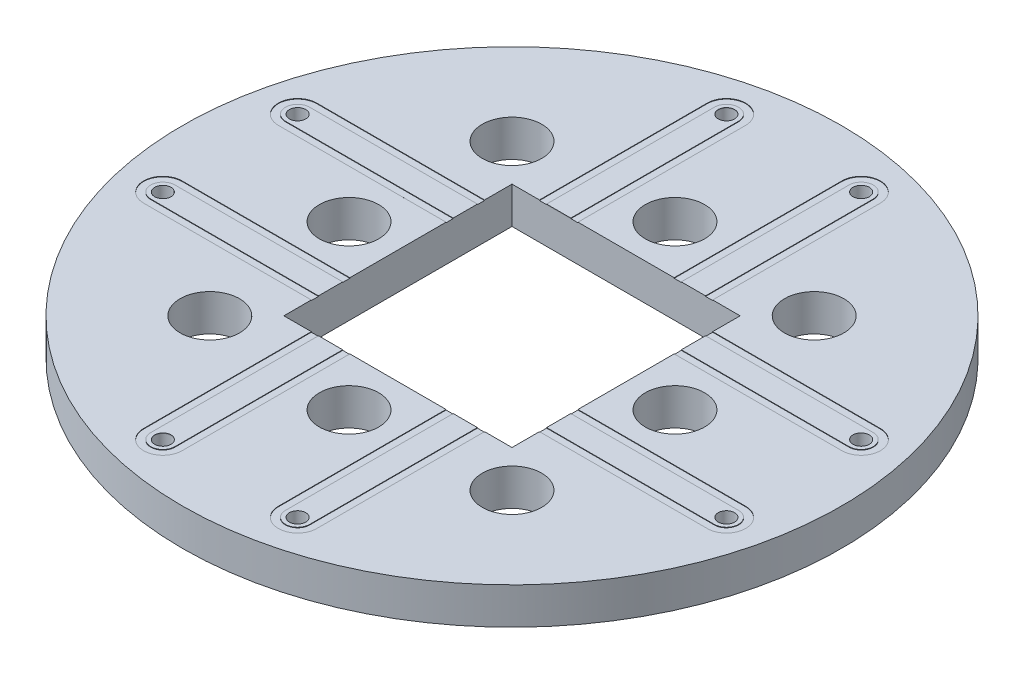
SolidWorks part; units mm, degrees
material "Ceramic Porcelain"
ref_plane "Front Plane" through (0, 0, 0) normal (0, 0, 1) x (1, 0, 0)
ref_plane "Top Plane" through (0, 0, 0) normal (0, 1, 0) x (1, 0, 0)
ref_plane "Right Plane" through (0, 0, 0) normal (1, 0, 0) x (0, 0, -1)
ref_axis "Y Axis" through (0, 0.0762, 0) along (0, -1, 0)
sketch "Boday Sketch" plane through (0, 0, 0) normal (0, 1, 0) x (1, 0, 0)
  circle A0 centre (0, 0) radius 11.557
  dimension "D1" = 23.114
extrude "Body" add sketch "Boday Sketch" against normal blind 1.27
sketch "Copper Sketch" plane through (0, 0, 0) normal (0, 1, 0) x (1, 0, 0)
  circle A0 centre (0, 0) radius 11.557
  dimension "D1" = 23.114
extrude "Copper" add sketch "Copper Sketch" along normal blind 0.0175
sketch "IO Hole Positions" plane through (0, 0, 0) normal (0, 1, 0) x (1, 0, 0)
  line L0 (-11.557, 0) -> (11.557, 0) construction
  circle A1 centre (0, 0) radius 11.557 construction
  point P1 (-2.3622, 9.8816)
  point P8 (-2.3622, -9.8816)
  dimension "D2" = 2.3622
sketch "Gap" plane through (0, 0, 0) normal (0, 1, 0) x (1, 0, 0)
  line L10 (-3.0372, 9.8816) -> (-3.0372, -9.8816)
  line L11 (-11.557, 0) -> (11.557, 0) construction
  line L12 (-3.0372, 0) -> (-1.6872, 0) construction
  line L13 (-1.6872, -9.8816) -> (-1.6872, 9.8816)
  arc A5 (-1.6872, 9.8816) -> (-3.0372, 9.8816) centre (-2.3622, 9.8816) ccw
  arc A6 (-1.6872, -9.8816) -> (-3.0372, -9.8816) centre (-2.3622, -9.8816) cw
  dimension "D1" = 0.675
sketch "Center Sketch" plane through (0, 0, 0) normal (0, 1, 0) x (1, 0, 0)
  line L6 (-2.7872, 9.8816) -> (-2.7872, -9.8816)
  line L7 (-11.557, 0) -> (11.557, 0) construction
  line L8 (-2.7872, 0) -> (-1.9372, 0) construction
  line L9 (-1.9372, -9.8816) -> (-1.9372, 9.8816)
  arc A3 (-1.9372, 9.8816) -> (-2.7872, 9.8816) centre (-2.3622, 9.8816) ccw
  arc A4 (-1.9372, -9.8816) -> (-2.7872, -9.8816) centre (-2.3622, -9.8816) cw
  dimension "D1" = 0.425
extrude "Gap Cut" cut sketch "Gap" along normal through all
extrude "Center" add sketch "Center Sketch" along normal blind 0.0175 separate body
sketch "IO Hole Sketch" plane through (0, 0, 0) normal (0, 1, 0) x (1, 0, 0)
  circle A1 centre (-2.3622, 9.8816) radius 0.287
  circle A3 centre (-2.3622, -9.8816) radius 0.287
  circle A4 centre (0, 0) radius 10.16 construction
  dimension "D1" = 0.574
  dimension "D2" = 0.574
  dimension "D3" = 20.32
  dimension "D4" = 2.3622
extrude "IO Hole" cut sketch "IO Hole Sketch" against normal through all and the other way through all
pattern_circular "Gap Cuts" count 4 over 360 about axis through (0, 0.0762, 0) along (0, -1, 0) of "Gap Cut"
pattern_circular "Centers" count 4 over 360 about axis through (0, 0.0762, 0) along (0, -1, 0) of "Center"
pattern_circular "IO Holes" count 4 over 360 about axis through (0, 0.0762, 0) along (0, -1, 0) of "IO Hole"
sketch "Pocket Sketch" plane through (0, 0, 0) normal (0, 1, 0) x (1, 0, 0)
  line L1 (-4, -4) -> (4, -4)
  line L2 (-4, -4) -> (-4, 4)
  line L3 (-4, 4) -> (4, 4)
  line L4 (4, -4) -> (4, 4)
  line L5 (-4, -4) -> (4, 4) construction
  line L6 (-4, 4) -> (4, -4) construction
  point P0 (0, 0)
  dimension "D1" = 8
  dimension "D2" = 8
extrude "Pocket" cut sketch "Pocket Sketch" against normal through all and the other way through all
sketch "Posts" plane through (0, 0, 0) normal (0, 1, 0) x (1, 0, 0)
  circle A0 centre (0, 5.715) radius 1.0414
  circle A8 centre (-5.2984, 5.2984) radius 1.0414
  point P0 (0, 5.715)
  point P4 (-5.2984, 5.2984)
  dimension "D2" = 2.0828
  dimension "D4" = 2.0828
  dimension "D1" = 5.715
  dimension "D3" = 7.493
  dimension "D5" = 5.715
extrude "Post Cut" cut sketch "Posts" against normal through all and the other way through all
pattern_circular "Post Cuts" count 4 over 360 about axis through (0, 0.0762, 0) along (0, -1, 0) of "Post Cut"
equation "\"mount_d\"= 0.91in"
equation "\"dieletric_h\"= 0.05in"
equation "\"D1@Boday Sketch\" = \"mount_d\""
equation "\"D1@Body\" = \"dieletric_h\""
equation "\"screw_inner_r\"= 0.415in"
equation "\"io_r\"= 0.4in"
equation "\"io_hole_d\"= 0.574mm"
equation "\"W\"= 0.85mm"
equation "\"G\"= 0.25mm"
equation "\"copper_t\"= 17.5um"
equation "\"silicon_size\"= 8mm"
equation "\"D1@Center\" = \"copper_t\""
equation "\"D1@Copper\"=\"copper_t\""
equation "\"D1@Pocket Sketch\" = \"silicon_size\""
equation "\"D2@Pocket Sketch\" = \"silicon_size\""
equation "\"post_r1\" = 0.225in"
equation "\"post_r2\" = 0.295in"
equation "\"D1@Posts\"=\"post_r1\""
equation "\"post_hole_size\"= 0.082in"
equation "\"D2@Posts\"=\"post_hole_size\""
equation "\"D3@Posts\"=\"post_r2\""
equation "\"D4@Posts\"=\"post_hole_size\""
equation "\"io_x\"= 0.093in"
equation "\"D1@IO Hole Positions\"=\"io_r\""
equation "\"D2@IO Hole Positions\"=\"io_x\""
equation "\"D1@IO Hole Sketch\"=\"io_hole_d\""
equation "\"D2@IO Hole Sketch\"=\"io_hole_d\""
equation "\"D1@Gap\"= \"W\" / 2 + \"G\""
equation "\"D1@Center Sketch\"=\"W\" / 2"
equation "\"D5@Posts\"=\"post_r1\""
equation "\"D4@IO Hole Sketch\"=\"io_x\""
